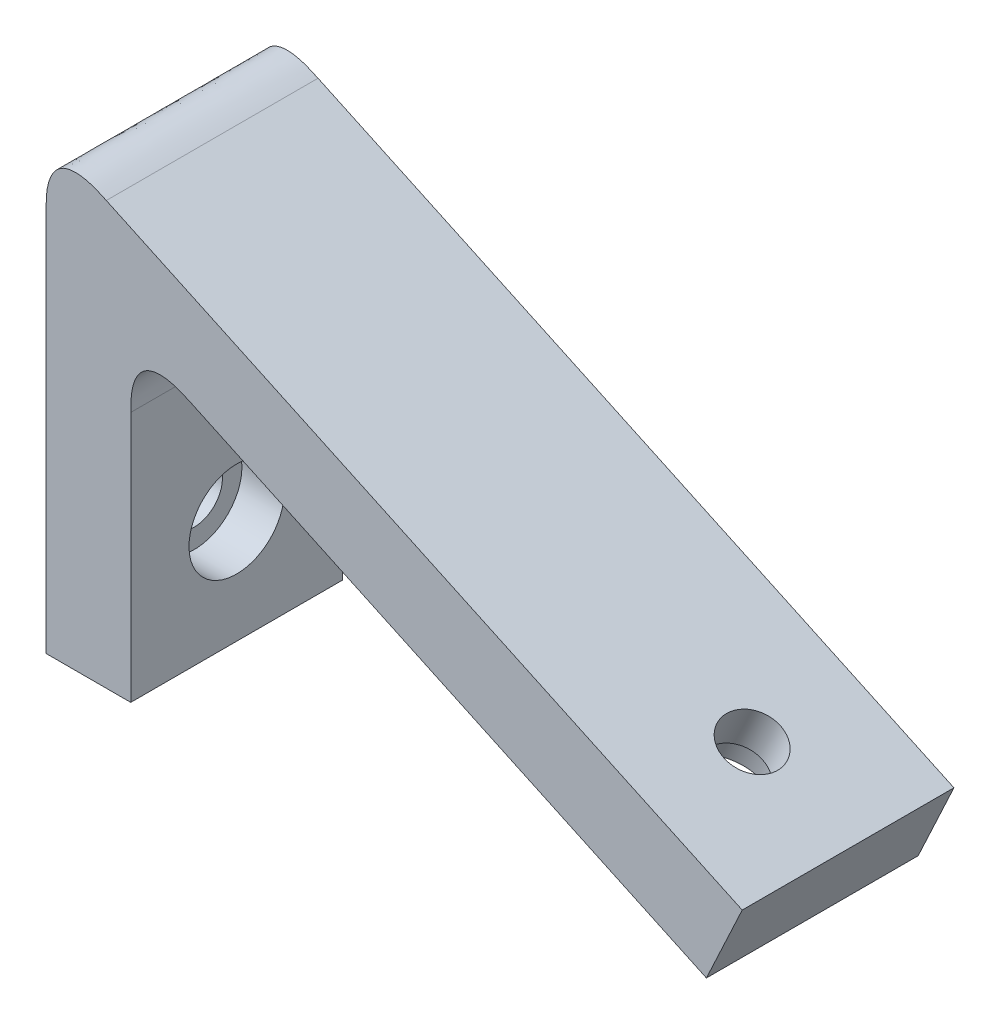
SolidWorks part; units mm, degrees
ref_plane "Front Plane" through (0, 0, 0) normal (0, 0, 1) x (1, 0, 0)
ref_plane "Top Plane" through (0, 0, 0) normal (0, 1, 0) x (1, 0, 0)
ref_plane "Right Plane" through (0, 0, 0) normal (1, 0, 0) x (0, 0, -1)
sketch "Sketch1" plane through (0, 0, 0) normal (0, 0, 1) x (1, 0, 0)
  line L0 (0, 0) -> (0, 54.048)
  line L1 (0, 54.048) -> (83.5145, 15.1046)
  line L2 (83.5145, 15.1046) -> (79.2207, 5.8965)
  line L3 (79.2207, 5.8965) -> (10.16, 38.1)
  line L4 (10.16, 38.1) -> (10.16, 0)
  line L5 (10.16, 0) -> (0, 0)
  dimension "D1" = 38.1
  dimension "D2" = 76.2
  dimension "D3" = 65
  dimension "D4" = 10.16
  dimension "D5" = 10.16
extrude "Boss-Extrude1" add sketch "Sketch1" along normal blind 25.4 contours L5 L4 L3 L2 L1 L0 region at (0.9948, 27.024, 0)
sketch "Sketch2" plane through (0, 0, 0) normal (-1, 0, 0) x (0, 0, 1)
  line L0 (0, 12.7) -> (25.4, 12.7) construction
  line L1 (0, 0) -> (0, 54.048) construction
  line L2 (25.4, 0) -> (25.4, 54.048) construction
  line L3 (25.4, 0) -> (0, 0) construction
  point P6 (12.7, 12.7)
  dimension "D1" = 12.7
sketch "Sketch3" plane through (20.7016, 44.3947, 0) normal (0.4226, 0.9063, 0) x (0.9063, -0.4226, 0)
  line L0 (56.6063, 0) -> (56.6063, -25.4) construction
  line L1 (-22.8417, 0) -> (69.3063, 0) construction
  line L2 (-22.8417, -25.4) -> (69.3063, -25.4) construction
  line L3 (69.3063, -25.4) -> (69.3063, 0) construction
  point P6 (56.6063, -12.7)
  dimension "D1" = 12.7
hole_wizard "1/4 Clearance Hole1" positions "Sketch4" profile "Sketch5" hole size "1/4" standard "ANSI Inch"
sketch "Sketch4" plane through (0, 0, 0) normal (-1, 0, 0) x (0, 0, 1)
  point P0 (12.7, 12.7)
sketch "Sketch5" plane through (0, 12.7, 12.7) normal (0, 1, 0) x (0, 0, 1)
  line L0 (0, 0) -> (0, 12.1898)
  line L1 (0, 12.1898) -> (3.3782, 10.16)
  line L2 (3.3782, 10.16) -> (3.3782, 0)
  line L5 (3.3782, 0) -> (0, 0)
  line L10 (0, 12.1898) -> (-3.3782, 10.16) construction
  line L11 (0, -6.35) -> (0, 107.95) construction
  dimension "Hole Dia." = 6.7564
  dimension "Hole Depth" = 10.16
  dimension "Drill Angle" = 118
hole_wizard "1/4 Clearance Hole2" positions "Sketch6" profile "Sketch7" hole size "1/4" standard "ANSI Inch"
sketch "Sketch6" plane through (20.7016, 44.3947, 0) normal (0.4226, 0.9063, 0) x (0.9063, -0.4226, 0)
  point P0 (56.6063, -12.7)
sketch "Sketch7" plane through (72.0043, 20.4718, 12.7) normal (0, 0, 1) x (-0.9063, 0.4226, 0)
  line L0 (0, 0) -> (0, 12.1898)
  line L1 (0, 12.1898) -> (3.3782, 10.16)
  line L2 (3.3782, 10.16) -> (3.3782, 0)
  line L5 (3.3782, 0) -> (0, 0)
  line L10 (0, 12.1898) -> (-3.3782, 10.16) construction
  line L11 (0, -6.35) -> (0, 107.95) construction
  dimension "Hole Dia." = 6.7564
  dimension "Hole Depth" = 10.16
  dimension "Drill Angle" = 118
fillet "Fillet1" radius 5.08 2 edges at (10.16, 38.1, 12.7) (0, 54.048, 12.7) curvature continuous yes
sketch "Sketch8" plane through (16.4078, 35.1866, 0) normal (-0.4226, -0.9063, 0) x (0.9063, -0.4226, 0)
  circle A0 centre (56.6063, 12.7) radius 5.715
  dimension "D1" = 11.43
extrude "Cut-Extrude1" cut sketch "Sketch8" against normal blind 5.08
sketch "Sketch9" plane through (10.16, 0, 0) normal (1, 0, 0) x (0, 0, -1)
  line L0 (0, 12.7) -> (-25.4, 12.7) construction
  circle A0 centre (-12.7, 12.7) radius 5.715
  dimension "D1" = 11.43
extrude "Cut-Extrude2" cut sketch "Sketch9" against normal blind 5.08
